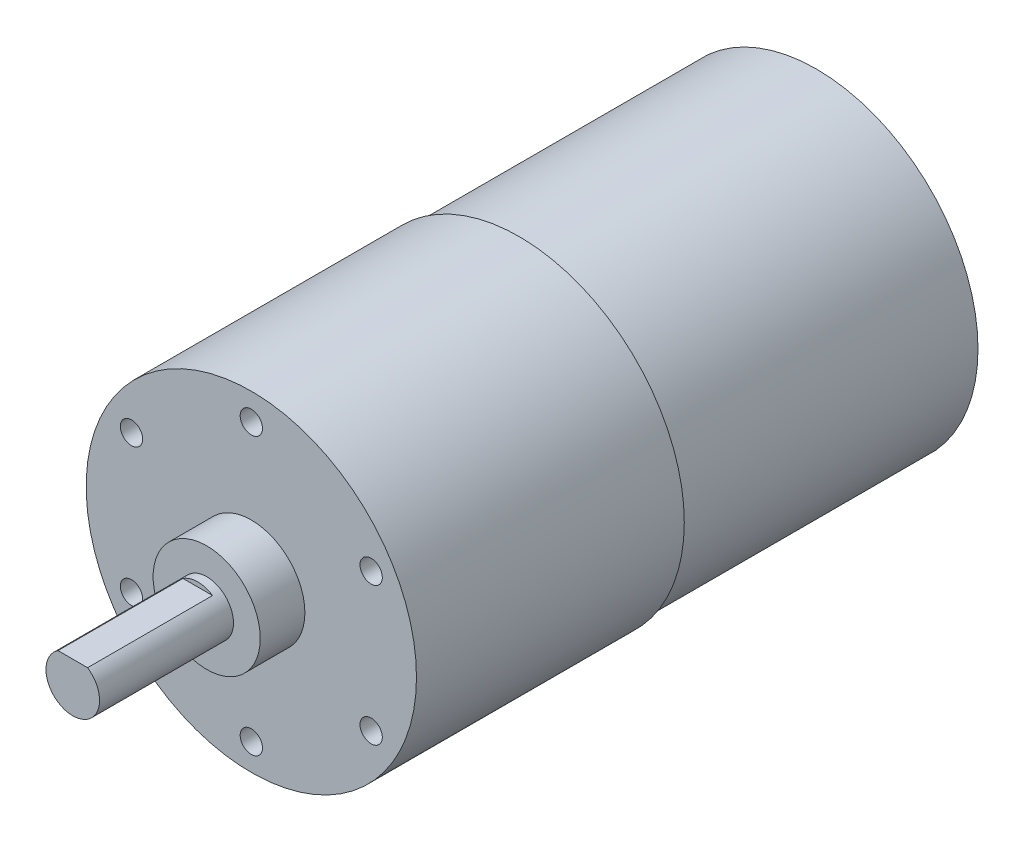
SolidWorks part; units mm, degrees
ref_plane "Front Plane" through (0, 0, 0) normal (0, 0, 1) x (1, 0, 0)
ref_plane "Top Plane" through (0, 0, 0) normal (0, 1, 0) x (1, 0, 0)
ref_plane "Right Plane" through (0, 0, 0) normal (1, 0, 0) x (0, 0, -1)
sketch "Sketch1" plane through (0, 0, 0) normal (0, 0, 1) x (1, 0, 0)
  circle A0 centre (0, 0) radius 18.5
  dimension "D1" = 37
extrude "Boss-Extrude1" add sketch "Sketch1" along normal blind 30
sketch "Sketch2" plane through (0, 0, 0) normal (0, 0, -1) x (-1, 0, 0)
  circle A0 centre (0, 0) radius 18.1
  dimension "D1" = 36.2
extrude "Boss-Extrude2" add sketch "Sketch2" along normal blind 33.3
sketch "Sketch3" plane through (0, 0, 30) normal (0, 0, 1) x (1, 0, 0)
  circle A0 centre (0, 0) radius 6
  dimension "D1" = 12
extrude "Boss-Extrude3" add sketch "Sketch3" along normal blind 5
sketch "Sketch4" plane through (0, 0, 35) normal (0, 0, 1) x (1, 0, 0)
  circle A0 centre (0, 0) radius 3
  dimension "D1" = 6
extrude "Boss-Extrude4" add sketch "Sketch4" along normal blind 1
sketch "Sketch5" plane through (0, 0, 36) normal (0, 0, 1) x (1, 0, 0)
  line L1 (-1.6583, 2.5) -> (1.6583, 2.5)
  arc A0 (-1.6583, 2.5) -> (1.6583, 2.5) centre (0, 0) ccw
  circle A1 centre (0, 0) radius 3 construction
  point P5 (0, 2.5)
  point P6 (0, -3)
  dimension "D1" = 5.5
extrude "Boss-Extrude5" add sketch "Sketch5" along normal blind 14
sketch "Sketch10" plane through (0, 0, 30) normal (0, 0, 1) x (1, 0, 0)
  point P0 (0, 0)
hole_wizard "M3x0.5 Tapped Hole1" positions "Sketch11" profile "Sketch12" tap size "M3x0.5" standard "ANSI Metric"
sketch "Sketch11" plane through (0, 0, 30) normal (0, 0, 1) x (1, 0, 0)
  line L0 (0, 0) -> (0, 15.5) construction
  point P0 (0, 15.5)
  point P8 (13.4234, 7.75)
  point P9 (13.4234, -7.75)
  point P10 (0, -15.5)
  point P11 (-13.4234, -7.75)
  point P12 (-13.4234, 7.75)
  dimension "D3" = 15.5
  dimension "D2" = 6
sketch "Sketch12" plane through (0, 15.5, 30) normal (1, 0, 0) x (0, -1, 0)
  line L0 (0, 0) -> (0, 6.7511)
  line L1 (0, 6.7511) -> (1.25, 6)
  line L2 (1.25, 6) -> (1.25, 0)
  line L5 (1.25, 0) -> (0, 0)
  line L10 (0, 6.7511) -> (-1.25, 6) construction
  line L11 (0, -6.35) -> (0, 107.95) construction
  dimension "Tap Drill Dia." = 2.5
  dimension "Tap Drill Depth" = 6
  dimension "Drill Angle" = 118
cosmetic thread "Hole Thread8" parameters "D1"=6, "D2"=3
cosmetic thread "Hole Thread9" parameters "D1"=6, "D2"=3
cosmetic thread "Hole Thread10" parameters "D1"=6, "D2"=3
cosmetic thread "Hole Thread11" parameters "D1"=6, "D2"=3
cosmetic thread "Hole Thread12" parameters "D1"=6, "D2"=3
cosmetic thread "Hole Thread13" parameters "D1"=6, "D2"=3
equation "\"PCB Width\"= 1940mil"
equation "\"PCB Height\"= 2210mil"
equation "\"PCB Thickness\"= 63mil"
equation "\"Motor Body Front Diameter\"= 37mm"
equation "\"Motor Body Front Length\"= 30mm"
equation "\"Motor Bearing Length\"= 5mm"
equation "\"Motor Body Back Length\"= 33.3mm"
equation "\"Motor PCR\"= 31mm / 2"
equation "\"Large PVC Fittings Wall Thickness\"= 15in / 64"
equation "\"Large PVC Pipe Outer Diameter\"= 3.5in"
equation "\"Box Width\"= 2 * \"Motor Bearing Length\" + \"Motor Body Front Length\" + \"Motor Body Back Length\" + 0.5in"
equation "\"Box Hole Center to Edge Distance\"= 300mil"
equation "\"Box Ceiling and Floor Thickness\"= 2 * \"Box Hole Center to Edge Distance\""
equation "\"Box Height\"= 2 * \"Box Ceiling and Floor Thickness\" + \"PCB Height\" + 0.5in"
equation "\"Box Back Depth\"= \"Large PVC Fittings Wall Thickness\" + \"Large PVC Pipe Outer Diameter\" / 2 + \"Motor Body Front Diameter\" / 2"
equation "\"D1@Sketch1\"=\"Motor Body Front Diameter\""
equation "\"D1@Boss-Extrude1\"=\"Motor Body Front Length\""
equation "\"D1@Boss-Extrude2\"=\"Motor Body Back Length\""
equation "\"D1@Boss-Extrude3\"=\"Motor Bearing Length\""
equation "\"D3@Sketch11\"=\"Motor PCR\""
